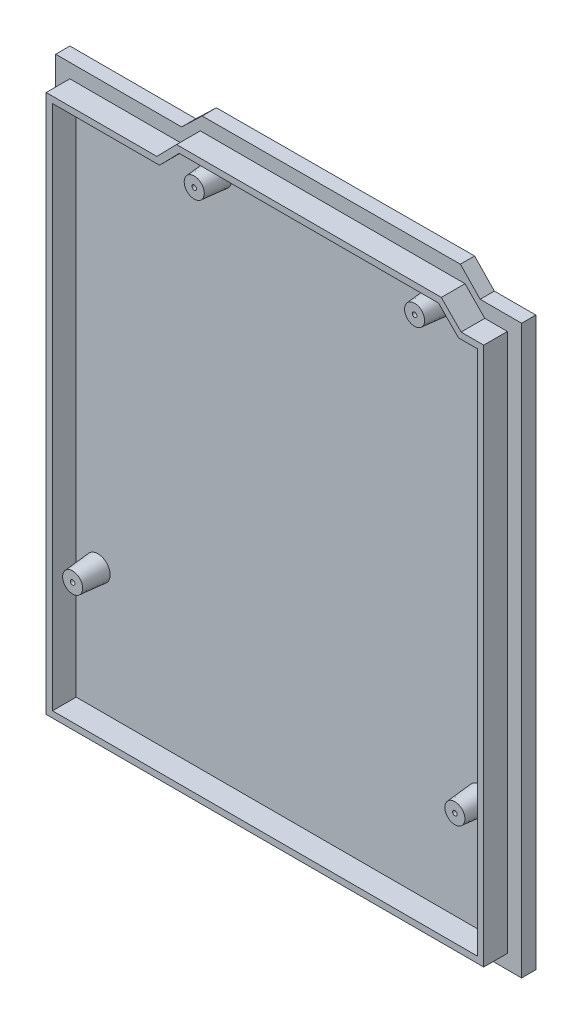
SolidWorks part; units mm, degrees
ref_plane "Front Plane" through (0, 0, 0) normal (1, 0, 0) x (0, 1, 0)
ref_plane "Top Plane" through (0, 0, 0) normal (0, 0, 1) x (0, 1, 0)
ref_plane "Right Plane" through (0, 0, 0) normal (0, 1, 0) x (-1, 0, 0)
sketch "Sketch1" plane through (0, 0, 0) normal (0, 0, 1) x (0, 1, 0)
  line L9 (40.6099, 53.4526) -> (-31.1901, 53.4526)
  line L10 (-31.1901, 53.4526) -> (-31.1901, -5.5474)
  line L11 (-31.1901, -5.5474) -> (40.6099, -5.5474)
  line L13 (43.1099, 34.9026) -> (43.2099, 2.2026)
  line L17 (40.6099, -5.5474) -> (40.6099, -0.2974)
  line L18 (40.6099, -0.2974) -> (43.2099, 2.2026)
  line L21 (43.1099, 34.9026) -> (40.6099, 37.5026)
  line L22 (40.6099, 37.5026) -> (40.6099, 53.4526)
extrude "Boss-Extrude1" add sketch "Sketch1" along normal blind 1.8
sketch "Sketch5" plane through (0, 0, 0) normal (0, 0, 1) x (0, 1, 0)
  line L0 (-28.5901, 50.8526) -> (-28.5901, -2.9474)
  line L1 (-28.5901, -2.9474) -> (38.0099, -2.9474)
  line L2 (38.0099, -2.9474) -> (38.0099, -0.5474)
  line L3 (38.0099, -0.5474) -> (40.5604, 1.9529)
  line L4 (40.5604, 1.9529) -> (40.5604, 34.8056)
  line L5 (40.5604, 34.8056) -> (38.0099, 37.3059)
  line L6 (38.0099, 37.3059) -> (38.0099, 50.8526)
  line L8 (38.0099, 50.8526) -> (-28.5901, 50.8526)
  line L19 (40.6099, 53.4526) -> (-31.1901, 53.4526) construction
  line L24 (-31.1901, 53.4526) -> (-31.1901, -5.5474) construction
  line L31 (40.6099, 37.5026) -> (40.6099, 53.4526) construction
  line L33 (40.6099, -5.5474) -> (40.6099, -0.2974) construction
  line L34 (43.2099, 2.2026) -> (43.1099, 34.9026) construction
  line L35 (-31.1901, -5.5474) -> (40.6099, -5.5474) construction
  point P19 (40.5604, 18.3793)
  dimension "D1" = 2.6
  dimension "D2" = 2.6
  dimension "D3" = 2.6
  dimension "D4" = 2.6
  dimension "D5" = 2.6
  dimension "D6" = 2.6
extrude "Extrude-Thin1" add sketch "Sketch5" along normal blind 3 from surface thin starting at face at (-21.2651, 23.2974, 1.8) thin type one direction wall 0.8
sketch "Sketch7" plane through (0, 0, 1.8) normal (0, 0, 1) x (1, 0, 0)
  line L1 (2.9474, 38.0099) -> (0.5474, 38.0099) construction
  line L2 (-34.8056, 40.5604) -> (-1.9529, 40.5604) construction
  line L3 (2.9474, 38.0099) -> (2.9474, -28.5901) construction
  line L4 (-50.8526, 38.0099) -> (-50.8526, -28.5901) construction
  line L5 (-50.8526, 38.0099) -> (-37.3059, 38.0099) construction
  circle A0 centre (-4.8026, 37.9604) radius 1.55
  circle A1 centre (-32.7026, 37.9604) radius 1.55
  circle A2 centre (0.2974, -14.1401) radius 1.55
  circle A3 centre (-48.1026, -13.0401) radius 1.55
  dimension "D1" = 3.1
  dimension "D6" = 2.75
  dimension "D2" = 2.6
  dimension "D3" = 7.75
  dimension "D4" = 0
  dimension "D5" = 27.9
  dimension "D7" = 2.65
  dimension "D8" = 52.15
  dimension "D9" = 51.05
extrude "Extrude-Thin2" add sketch "Sketch7" along normal blind 3.2 draft 5 thin thin type one direction reverse wall 1.54
